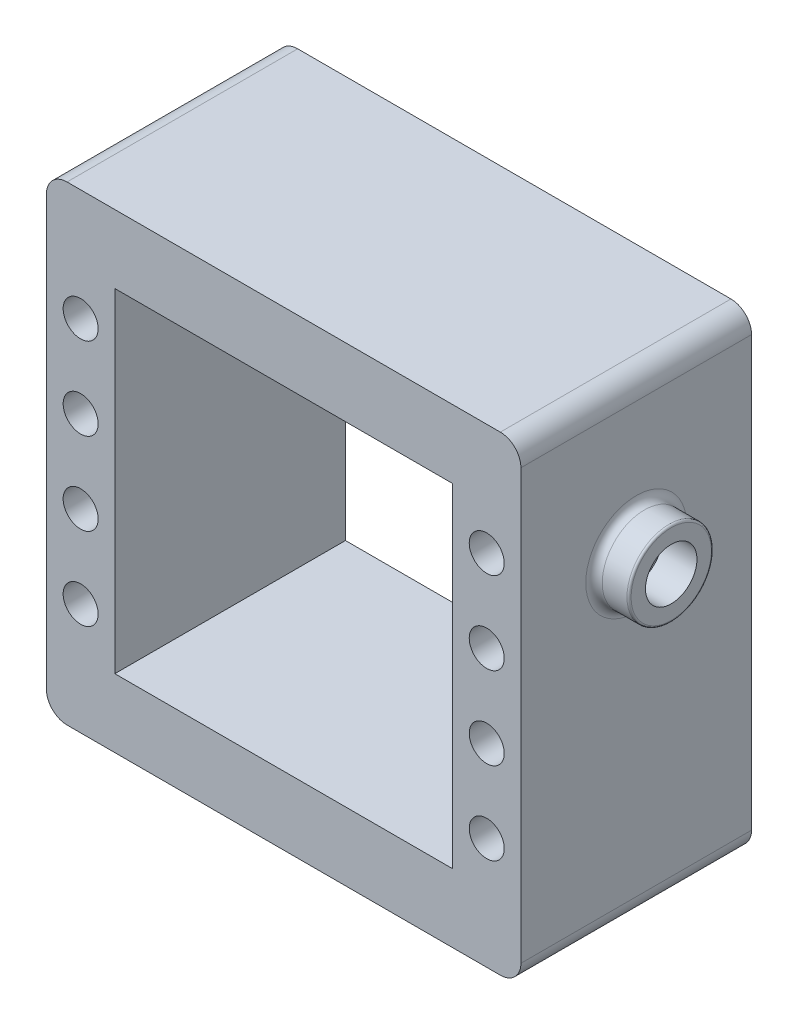
SolidWorks part; units mm, degrees
ref_plane "Front Plane" through (0, 0, 0) normal (0, 0, 1) x (1, 0, 0)
ref_plane "Top Plane" through (0, 0, 0) normal (0, 1, 0) x (1, 0, 0)
ref_plane "Right Plane" through (0, 0, 0) normal (1, 0, 0) x (0, 0, -1)
sketch "Sketch1" plane through (0, 0, 0) normal (0, 0, 1) x (1, 0, 0)
  line L0 (-8.3, -8.3) -> (49.3, -8.3)
  line L1 (0, 0) -> (41, 0)
  line L2 (0, 0) -> (0, 40.5)
  line L3 (0, 40.5) -> (41, 40.5)
  line L4 (41, 0) -> (41, 40.5)
  line L5 (49.3, -8.3) -> (49.3, 48.8)
  line L6 (-8.3, 48.8) -> (49.3, 48.8)
  line L7 (-8.3, -8.3) -> (-8.3, 48.8)
  line L8 (20.5, 48.8) -> (20.5, -8.3) construction
  line L9 (0, 20.25) -> (-8.3, 20.25) construction
  line L10 (-4.15, 20.25) -> (-4.15, 25.25) construction
  line L11 (-4.15, 25.25) -> (-4.15, 35.25) construction
  circle A0 centre (-4.15, 25.25) radius 2.125
  circle A1 centre (-4.15, 35.25) radius 2.125
  circle A2 centre (-4.15, 5.25) radius 2.125
  circle A3 centre (-4.15, 15.25) radius 2.125
  circle A4 centre (45.15, 15.25) radius 2.125
  circle A5 centre (45.15, 5.25) radius 2.125
  circle A6 centre (45.15, 35.25) radius 2.125
  circle A7 centre (45.15, 25.25) radius 2.125
  dimension "D4" = 5
  dimension "D5" = 4.25
  dimension "D1" = 41
  dimension "D2" = 40.5
  dimension "D6" = 10
  dimension "D3" = 8.3
extrude "Boss-Extrude1" add sketch "Sketch1" along normal blind 28
fillet "Fillet1" radius 2.5 4 edges at (49.3, 48.8, 14) (49.3, -8.3, 14) (-8.3, -8.3, 14) (-8.3, 48.8, 14)
sketch "Sketch2" plane through (49.3, 0, 0) normal (-1, 0, 0) x (0, 0, 1)
  line L0 (28, 30.25) -> (0, 30.25) construction
  line L1 (28, 46.3) -> (28, -5.8) construction
  line L2 (0, 46.3) -> (0, -5.8) construction
  circle A0 centre (14, 30.25) radius 3.125
  circle A1 centre (14, 30.25) radius 5.125
  dimension "D1" = 6.25
  dimension "D2" = 38.55
  dimension "D3" = 2
extrude "Boss-Extrude2" add sketch "Sketch2" against normal blind 4.25
fillet "Fillet2" radius 1 1 edges at (49.3, 30.25, 19.125)
fillet "Fillet3" radius 0.25 1 edges at (53.55, 30.25, 19.125)
sketch "Sketch3" plane through (49.3, 0, 0) normal (1, 0, 0) x (0, 0, -1)
  circle A0 centre (-14, 30.25) radius 1.7
  dimension "D1" = 3.4
extrude "Cut-Extrude1" cut sketch "Sketch3" against normal up to next
sketch "Sketch5" plane through (41, 0, 0) normal (-1, 0, 0) x (0, 0, 1)
  circle A0 centre (14, 30.25) radius 3.125
  dimension "D1" = 6.25
ref_plane "Plane1" through (43.5, 0, 0) normal (-1, 0, 0) x (0, 0, 1)
sketch "Sketch6" plane through (43.5, 0, 0) normal (-1, 0, 0) x (0, 0, 1)
  circle A0 centre (14, 30.25) radius 1.7
  circle A1 centre (14, 30.25) radius 1.7
loft "Cut-Loft1" cut profiles "Sketch5", "Sketch6" connector at (41, 30.25, 17.125) connector at (43.5, 30.25, 15.7)
